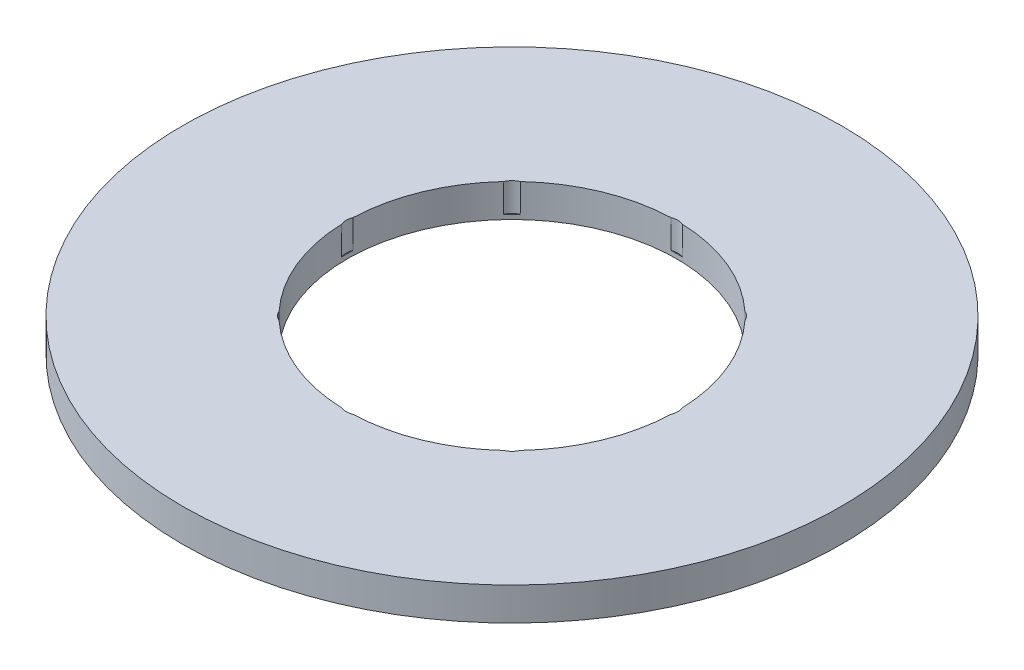
SolidWorks part; units mm, degrees
ref_plane "Front Plane" through (0, 0, 0) normal (0, 0, 1) x (1, 0, 0)
ref_plane "Top Plane" through (0, 0, 0) normal (0, 1, 0) x (1, 0, 0)
ref_plane "Right Plane" through (0, 0, 0) normal (1, 0, 0) x (0, 0, -1)
sketch "Sketch1" plane through (0, 0, 0) normal (0, 1, 0) x (1, 0, 0)
  circle A0 centre (0, 0) radius 100
  dimension "FLANGE_OD" = 200
extrude "Boss-Extrude1" add sketch "Sketch1" along normal blind 10
sketch "Sketch2" plane through (0, 0, 0) normal (0, 1, 0) x (1, 0, 0)
  circle A0 centre (0, 0) radius 50
  dimension "BORE_D" = 100
extrude "Cut-Extrude1" cut sketch "Sketch2" along normal through all
sketch "Sketch3" plane through (0, 10, 0) normal (0, 1, 0) x (1, 0, 0)
  circle A0 centre (0, 0) radius 45.3849 construction
  circle A1 centre (-45.3849, 0) radius 4.9221
  dimension "BOLT_D" = 9.8441
  dimension "BOLT_PCD" = 90.7699
extrude "Cut-Extrude2" cut sketch "Sketch3" against normal blind 8.6269
pattern_circular "CirPattern1" count 8 over 360 about axis through (0, 0, 0) along (0, 1, 0) of "Cut-Extrude2"
